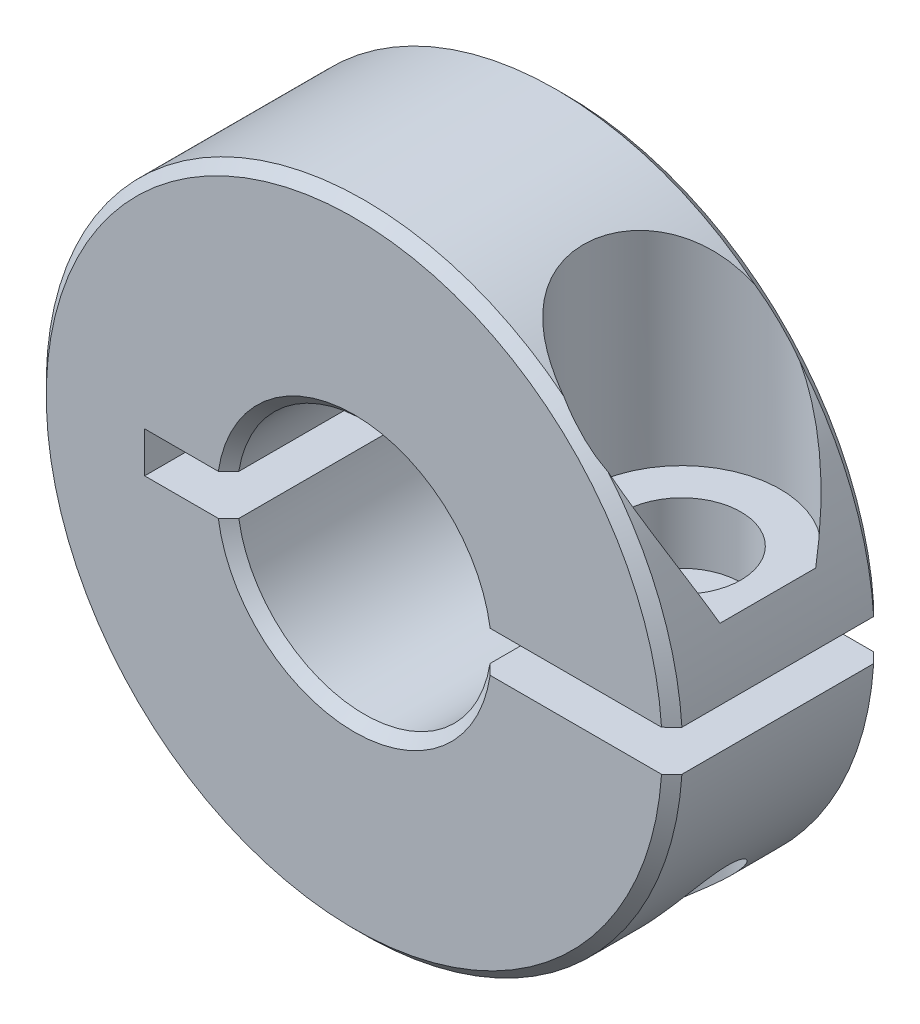
SolidWorks part; units mm, degrees
ref_plane "Front" through (0, 0, 0) normal (0, 0, 1) x (1, 0, 0)
ref_plane "Top" through (0, 0, 0) normal (0, 1, 0) x (1, 0, 0)
ref_plane "Right" through (0, 0, 0) normal (1, 0, 0) x (0, 0, -1)
ref_axis "side-side" through (80.9, 0, 0) along (-1, 0, 0)
ref_axis "up-down" through (0, 50, 0) along (0, -1, 0)
ref_axis "front-back" through (0, 0, -80.9) along (0, 0, 1)
sketch "Sketch1" plane through (0, 0, 0) normal (0, 0, 1) x (1, 0, 0)
  line L0 (-7.8422, 0) -> (0, 0) construction
  line L1 (-7.8422, 0.762) -> (-4.7011, 0.762)
  line L2 (-7.8422, 0.762) -> (-7.8422, -0.762)
  line L3 (-7.8422, -0.762) -> (-4.7011, -0.762)
  line L4 (4.7011, -0.762) -> (11.8818, -0.762)
  line L5 (4.7011, 0.762) -> (11.8818, 0.762)
  arc A0 (11.8818, 0.762) -> (11.8818, -0.762) centre (0, 0) ccw
  arc A1 (4.7011, 0.762) -> (-4.7011, 0.762) centre (0, 0) ccw
  arc A2 (-4.7011, -0.762) -> (4.7011, -0.762) centre (0, 0) ccw
  dimension "D1" = 9.525
  dimension "D2" = 23.8125
  dimension "D3" = 1.524
  dimension "D4" = 4.064
extrude "Boss-Extrude1" add sketch "Sketch1" along normal mid plane 7.9375
hole_wizard "#8-32 Tapped Hole1" positions "Sketch2" profile "Sketch4" tap size "#8-32" standard "ANSI Inch" end condition through all
sketch "Sketch2" plane through (0, -0.762, 0) normal (0, 1, 0) x (1, 0, 0)
  line L0 (11.8818, -3.9688) -> (4.7011, 3.9688) construction
  point P0 (8.2915, 0)
  point P6 (0, 0)
sketch "Sketch4" plane through (8.2915, -0.762, 0) normal (1, 0, 0) x (0, 0, 1)
  line L0 (0, 0) -> (0, 11.1442)
  line L1 (0, 11.1442) -> (1.7272, 11.1442)
  line L2 (1.7272, 11.1442) -> (1.7272, 0)
  line L5 (1.7272, 0) -> (0, 0)
  line L11 (0, -6.35) -> (0, 107.95) construction
  dimension "Thread Major Dia." = 3.4544
  dimension "Thru Tap Drill Depth" = 11.1442
sketch "Sketch5" plane through (0, 0.762, 0) normal (0, -1, 0) x (1, 0, 0)
  circle A0 centre (8.2915, 0) radius 1.27
  dimension "D1" = 2.54
chamfer "Chamfer1" distance 0.381 angle 45 6 edges at (-11.9062, 0, -3.9688) (0, -4.7625, -3.9688) (0, 4.7625, -3.9688) (-11.9062, 0, 3.9688) (0, -4.7625, 3.9688) (0, 4.7625, 3.9688)
sketch "Sketch10" plane through (0, 0, 0) normal (0, 0, 1) x (1, 0, 0)
  line L0 (8.2915, -0.762) -> (8.2915, -11.9948) construction
  line L1 (5.0867, 0.762) -> (11.5, 0.762) construction
  line L2 (8.2934, 0.762) -> (10.5013, 0.762)
  line L3 (8.2934, 0.762) -> (8.2934, 11.9062)
  line L4 (8.2934, 11.9062) -> (11.9745, 11.9062)
  line L5 (10.5013, 0.762) -> (10.5013, 3.048)
  line L7 (10.5013, 3.048) -> (11.9745, 3.048)
  line L10 (11.9745, 3.048) -> (11.9745, 11.9062)
  arc A0 (11.8818, -0.762) -> (-11.8818, 0.762) centre (0, 0) ccw construction
  dimension "D1" = 7.366
  dimension "D2" = 4.4196
  dimension "D3" = 2.286
revolve "Cut-Revolve1" cut sketch "Sketch10" angle 360 about L0
